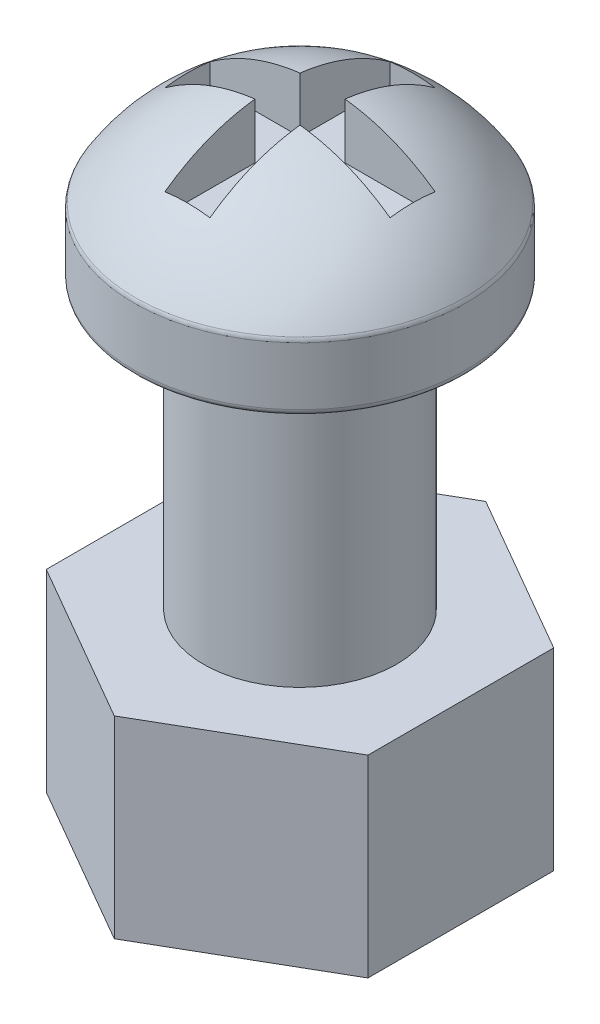
SolidWorks part; units mm, degrees
ref_plane "Front Plane" through (0, 0, 0) normal (0, 0, 1) x (1, 0, 0)
ref_plane "Top Plane" through (0, 0, 0) normal (0, 1, 0) x (1, 0, 0)
ref_plane "Right Plane" through (0, 0, 0) normal (1, 0, 0) x (0, 0, -1)
sketch "Sketch1" plane through (0, 0, 0) normal (0, 1, 0) x (1, 0, 0)
  line L1 (2.5, 1.4434) -> (0, 2.8868)
  line L2 (0, 2.8868) -> (-2.5, 1.4434)
  line L3 (-2.5, 1.4434) -> (-2.5, -1.4434)
  line L4 (-2.5, -1.4434) -> (0, -2.8868)
  line L5 (0, -2.8868) -> (2.5, -1.4434)
  line L6 (2.5, -1.4434) -> (2.5, 1.4434)
  circle A0 centre (0, 0) radius 2.5 construction
  circle A1 centre (0, 0) radius 1.5
  dimension "D1" = 3
  dimension "D2" = 5
extrude "Boss-Extrude1" add sketch "Sketch1" along normal blind 30 contours A1 | L5 L6 L1 L2 L3 L4 A1 region at (2.4236, 0, 0) region at (0, 0, 0)
extrude "Boss-Extrude2" add sketch "Sketch1<4>" against normal blind 6 contours A1 region at (0, 0, 0)
sketch "Sketch1<4>" plane through (0, 0, 0) normal (0, 1, 0) x (1, 0, 0) same geometry as "Sketch1"
sketch "Sketch3" plane through (0, 0, 0) normal (0, 0, 1) x (1, 0, 0)
  line L0 (1.5, -6) -> (1.5, 0) construction
  line L1 (0, 30) -> (1.5, 30)
  line L2 (0, 30) -> (0, 34.4)
  line L3 (0, 34.4) -> (1.5, 34.4)
  line L4 (1.5, 30) -> (1.5, 34.4)
  line L5 (0, 30) -> (0, 0) construction
  line L6 (1.5, 34.4) -> (3.6588, 34.4)
  line L7 (0, 34.4) -> (0, 36.9)
  line L8 (0, 30) -> (0, -6) construction
  line L9 (-1.5, -6) -> (1.5, -6) construction
  line L10 (0, 12) -> (3.9182, 12) construction
  line L11 (0, -10.4) -> (0, -12.9)
  line L12 (1.5, -10.4) -> (3.6588, -10.4)
  line L13 (1.5, -6) -> (1.5, -10.4)
  line L14 (0, -10.4) -> (1.5, -10.4)
  line L15 (0, -6) -> (0, -10.4)
  line L16 (0, -6) -> (1.5, -6)
  line L17 (2.5777, 35.4) -> (2.5777, 34.4)
  circle A0 centre (0, 33.9) radius 3
  circle A1 centre (2.4527, 35.4) radius 0.125
  circle A2 centre (0, -9.9) radius 3
  circle A3 centre (2.4527, -11.4) radius 0.125
  dimension "D2" = 0.25
  dimension "D5" = 6
  dimension "D1" = 4.4
  dimension "D3" = 1
  dimension "D4" = 0.5
revolve "Revolve1" add sketch "Sketch3" angle 360 about L8 region at (0.798, 30.5219, 0) region at (0.7353, 32.713, 0) region at (1.1363, 35.4777, 0) region at (2.4527, 35.4, 0)
ref_plane "Plane1" through (0, 40, 0) normal (0, 1, 0) x (1, 0, 0)
sketch "Sketch4" plane through (0, 40, 0) normal (0, 1, 0) x (1, 0, 0)
  line L1 (-1.75, -0.35) -> (1.75, -0.35)
  line L2 (-1.75, -0.35) -> (-1.75, 0.35)
  line L3 (-1.75, 0.35) -> (1.75, 0.35)
  line L4 (1.75, -0.35) -> (1.75, 0.35)
  line L5 (-1.75, -0.35) -> (1.75, 0.35) construction
  line L6 (-1.75, 0.35) -> (1.75, -0.35) construction
  line L7 (-0.35, -1.75) -> (0.35, -1.75)
  line L8 (-0.35, -1.75) -> (-0.35, 1.75)
  line L9 (-0.35, 1.75) -> (0.35, 1.75)
  line L10 (0.35, -1.75) -> (0.35, 1.75)
  line L11 (-0.35, -1.75) -> (0.35, 1.75) construction
  line L12 (-0.35, 1.75) -> (0.35, -1.75) construction
  point P0 (0, 0)
  point P6 (0, 0)
  dimension "D1" = 0.7
  dimension "D2" = 3.5
extrude "Cut-Extrude1" cut sketch "Sketch4" against normal blind 4 contours L7 L10 L1 L8 | L10 L1 L4 L3 | L3 L10 L9 L8 | L1 L8 L3 L2 | L1 L10 L3 L8 region at (-1.05, 40, 0) region at (0, 40, 0) region at (0, 40, 1.05) region at (1.05, 40, 0) region at (0, 40, -1.05)
fillet "Fillet1" radius 0.1 1 edges at (-2.5777, 34.4, 0)
sketch "Sketch5" plane through (0, -6, 0) normal (0, -1, 0) x (1, 0, 0)
  line L6 (2.5, 1.4434) -> (0, 2.8868)
  line L7 (0, 2.8868) -> (-2.5, 1.4434)
  line L8 (-2.5, 1.4434) -> (-2.5, -1.4434)
  line L9 (-2.5, -1.4434) -> (0, -2.8868)
  line L10 (0, -2.8868) -> (2.5, -1.4434)
  line L11 (2.5, -1.4434) -> (2.5, 1.4434)
  line L12 (2.5, 1.4434) -> (0, 2.8868)
  line L13 (0, 2.8868) -> (-2.5, 1.4434)
  line L14 (-2.5, 1.4434) -> (-2.5, -1.4434)
  line L15 (-2.5, -1.4434) -> (0, -2.8868)
  line L16 (0, -2.8868) -> (2.5, -1.4434)
  line L17 (2.5, -1.4434) -> (2.5, 1.4434)
  circle A0 centre (0, 0) radius 1.5 construction
  circle A1 centre (0, 0) radius 1.5
  dimension "D1" = 0
extrude "Boss-Extrude3" add sketch "Sketch5" against normal blind 3 separate body
sketch "Sketch6" plane through (0, -6, 0) normal (0, -1, 0) x (1, 0, 0)
  circle A0 centre (0, 0) radius 4.5352
extrude "Cut-Extrude2" cut sketch "Sketch6" against normal blind 33
